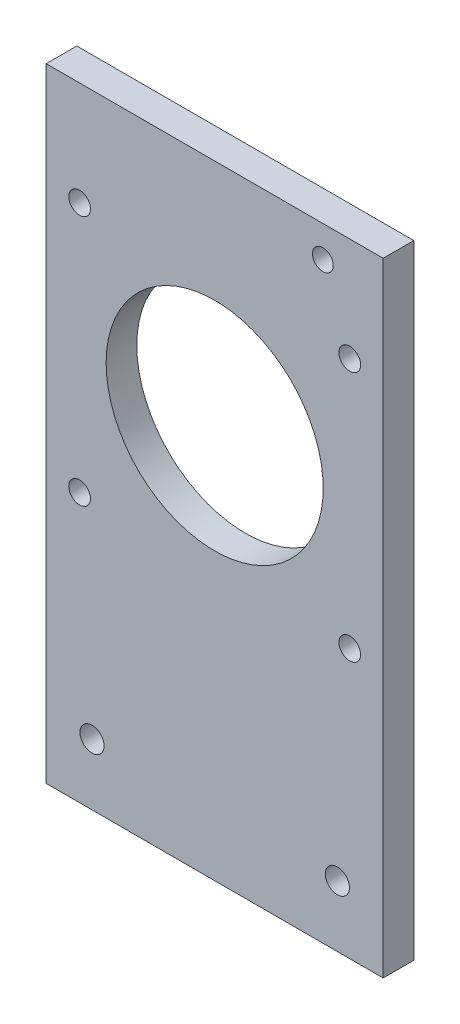
SolidWorks part; units mm, degrees
ref_plane "Front Plane" through (0, 0, 0) normal (0, 0, 1) x (1, 0, 0)
ref_plane "Top Plane" through (0, 0, 0) normal (0, 1, 0) x (1, 0, 0)
ref_plane "Right Plane" through (0, 0, 0) normal (1, 0, 0) x (0, 0, -1)
sketch "Sketch2" plane through (0, 0, 0) normal (0, 0, 1) x (1, 0, 0)
  line L0 (-55, 72.2) -> (55, 72.2) construction
  line L1 (-34.925, 0) -> (34.925, 0)
  line L2 (-34.925, 0) -> (-34.925, 81.7)
  line L3 (-34.925, 81.7) -> (34.925, 81.7) construction
  line L4 (34.925, 0) -> (34.925, 81.7)
  line L5 (0, 72.2) -> (0, 0) construction
  line L6 (0, 72.2) -> (0, 81.7) construction
  line L7 (-34.925, 25.4) -> (34.925, 25.4) construction
  line L10 (34.925, 114.2) -> (-34.925, 114.2) construction
  line L11 (34.925, 81.7) -> (34.925, 114.2)
  line L12 (34.925, 114.2) -> (-34.925, 114.2) construction
  line L13 (-34.925, 114.2) -> (-34.925, 81.7)
  line L14 (34.925, 114.2) -> (34.925, 129.2)
  line L15 (34.925, 129.2) -> (-34.925, 129.2)
  line L16 (-34.925, 114.2) -> (-34.925, 129.2)
  line L17 (-34.925, 25.4) -> (34.925, 25.4) construction
  circle A0 centre (-55, 72.2) radius 3 construction
  circle A1 centre (55, 72.2) radius 3 construction
  circle A2 centre (-55, 72.2) radius 15 construction
  circle A3 centre (55, 72.2) radius 15 construction
  circle A6 centre (0, 81.7) radius 22.5
  circle A7 centre (-55, 72.2) radius 15.6 construction
  point P6 (0, 0)
  dimension "D1" = 6
  dimension "D2" = 30
  dimension "D5" = 45
  dimension "D9" = 15
  dimension "D3" = 110
  dimension "D4" = 9.5
  dimension "D6" = 69.85
  dimension "D7" = 56.3
  dimension "D8" = 32.5
  dimension "D10" = 25.4
  dimension "D11" = 0.6
extrude "Boss-Extrude1" add sketch "Sketch2" along normal mid plane 6.35
sketch "Sketch3" plane through (0, 0, 3.175) normal (0, 0, 1) x (1, 0, 0)
  line L0 (34.925, 129.2) -> (-34.925, 129.2) construction
  line L1 (-34.925, 0) -> (-25.425, 0) construction
  line L2 (-34.925, 0) -> (-34.925, 12.7) construction
  line L3 (-34.925, 12.7) -> (-25.425, 12.7) construction
  line L4 (-25.425, 0) -> (-25.425, 12.7) construction
  line L5 (34.925, 0) -> (25.425, 0) construction
  line L6 (34.925, 0) -> (34.925, 12.7) construction
  line L7 (34.925, 12.7) -> (25.425, 12.7) construction
  line L8 (25.425, 0) -> (25.425, 12.7) construction
  line L10 (34.925, 0) -> (34.925, 129.2) construction
  circle A0 centre (-25.425, 12.7) radius 2.5
  circle A1 centre (25.425, 12.7) radius 2.5
  circle A2 centre (22.425, 122.7) radius 2.15
  dimension "D1" = 12.7
  dimension "D2" = 5
  dimension "D4" = 4.3
  dimension "D5" = 6.5
  dimension "D3" = 9.5
  dimension "D6" = 12.5
extrude "Cut-Extrude1" cut sketch "Sketch3" against normal through all both and the other way through all
sketch "Sketch4" plane through (0, 0, -3.175) normal (0, 0, -1) x (-1, 0, 0)
  circle A0 centre (-28, 107.7) radius 2.25 construction
  circle A1 centre (28, 107.7) radius 2.25 construction
  circle A2 centre (-28, 55.7) radius 2.25 construction
  circle A3 centre (28, 55.7) radius 2.25 construction
  circle A4 centre (-28, 107.7) radius 2.25
  circle A5 centre (28, 107.7) radius 2.25
  circle A6 centre (-28, 55.7) radius 2.25
  circle A7 centre (28, 55.7) radius 2.25
extrude "Cut-Extrude2" cut sketch "Sketch4" against normal through all both and the other way through all
